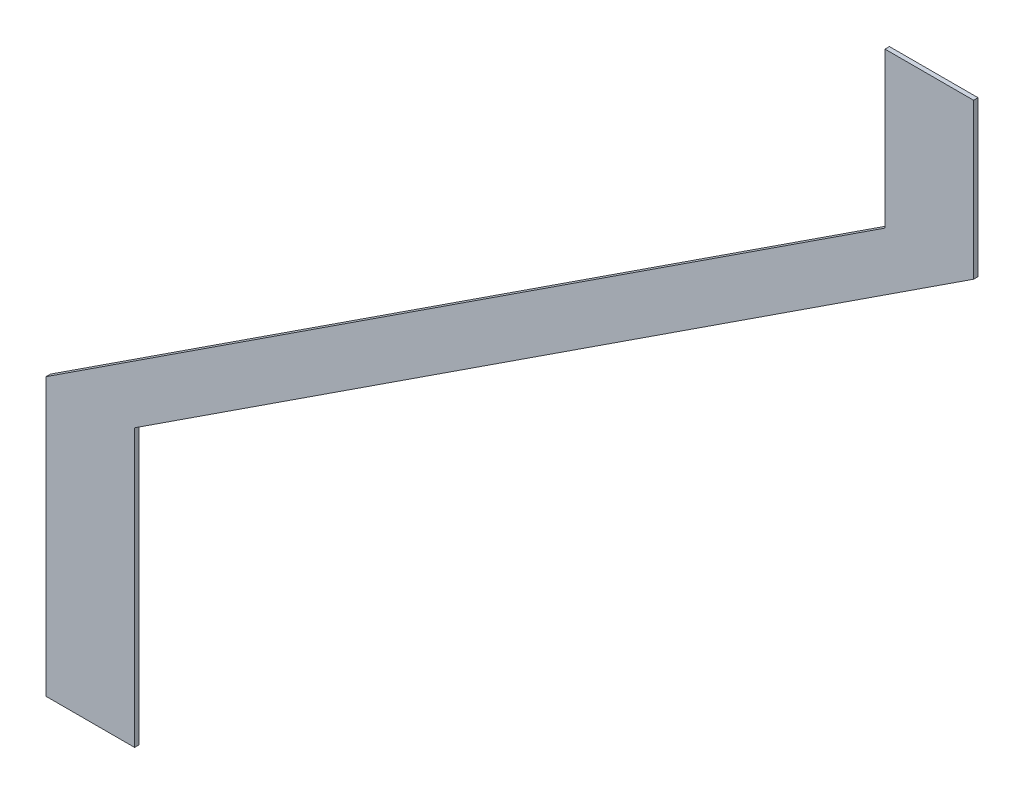
SolidWorks part; units mm, degrees
material "天然橡胶"
ref_plane "前视基准面" through (0, 0, 0) normal (0, 0, 1) x (1, 0, 0)
ref_plane "上视基准面" through (0, 0, 0) normal (0, 1, 0) x (1, 0, 0)
ref_plane "右视基准面" through (0, 0, 0) normal (1, 0, 0) x (0, 0, -1)
sketch "草图1" plane through (0, 0, 0) normal (0, 1, 0) x (1, 0, 0)
  line L0 (0, 1.5) -> (0, -1.5) construction
  line L1 (-991.5, 0) -> (991.5, 0) construction
  line L2 (0, -1.5) -> (-991.4989, -1.5) construction
  line L3 (0, -1.5) -> (991.4989, -1.5) construction
  line L4 (0, 0) -> (-701.0964, -701.0964) construction
  line L5 (-1011.2715, -1.5) -> (-1071.5, -1.5)
  circle A0 centre (0, 0) radius 991.5 construction
  arc A2 (-991.276, -21.0749) -> (-701.0964, -701.0964) centre (0, 0) ccw
  arc A3 (-1011.2715, -1.5) -> (-991.276, -21.0749) centre (-1011.2715, -21.5) cw
  dimension "D1" = 1983
  dimension "D5" = 20
  dimension "D2" = 3
  dimension "D3" = 45
  dimension "D4" = 80
ref_plane "基准面1" through (0, -495, 0) normal (0, 1, 0) x (1, 0, 0)
sketch "草图7" plane through (0, -495, 0) normal (0, 1, 0) x (1, 0, 0)
  line L0 (-1750, -2) -> (1750, -2) construction
  line L1 (-1650, -1750) -> (1650, -1750) construction
  line L2 (-1750, -1750) -> (-1750, 1650) construction
  line L3 (-1650, 1750) -> (1650, 1750) construction
  line L4 (1750, -1650) -> (1750, 1650) construction
  line L5 (-1750, -1750) -> (1750, 1750) construction
  line L6 (-1750, 1750) -> (1750, -1750) construction
  line L7 (-1750, -22) -> (-1750, -1650)
  line L8 (-1770, -2) -> (-1830, -2)
  arc A0 (-1750, -22) -> (-1770, -2) centre (-1770, -22) ccw
  arc A1 (-1750, 1650) -> (-1650, 1750) centre (-1650, 1650) cw construction
  arc A2 (1750, 1650) -> (1650, 1750) centre (1650, 1650) ccw construction
  arc A3 (1750, -1650) -> (1650, -1750) centre (1650, -1650) cw construction
  arc A4 (-1650, -1750) -> (-1750, -1650) centre (-1650, -1650) cw construction
  arc A5 (-1750, -1650) -> (-1720.7107, -1720.7107) centre (-1650, -1650) ccw
  point P0 (0, 0)
  dimension "D5" = 20
  dimension "D6" = 100
  dimension "D1" = 3500
  dimension "D2" = 3500
  dimension "D3" = 2
  dimension "D4" = 80
sketch "草图8" plane through (0, 0, 0) normal (0, 0, 1) x (1, 0, 0)
  line L0 (-1072.3529, 0) -> (-1830, -495)
  line L1 (-1011.2715, 0) -> (-1071.5, 0) construction
  line L2 (-1770, -495) -> (-1830, -495) construction
  line L3 (-1750, -495) -> (-992.3529, 0)
  line L4 (-1750, -495) -> (1750, -495) construction
  line L5 (0, 0) -> (-991.4989, 0) construction
  line L6 (-991.5, 0) -> (991.5, 0) construction
  line L7 (-1650, -495) -> (-1750, -495) construction
  line L8 (-1830, -495) -> (-1830, -745)
  line L9 (-1830, -745) -> (-1750, -745)
  line L10 (-1750, -745) -> (-1750, -495)
  line L11 (-1072.3529, 0) -> (-1072.3529, 140)
  line L12 (-1072.3529, 140) -> (-992.3529, 140)
  line L13 (-992.3529, 140) -> (-992.3529, 0)
  dimension "D1" = 80
  dimension "D2" = 80
  dimension "D3" = 250
  dimension "D4" = 140
base flange "基体-法兰1" sketch "草图8" thickness 4 reverse thickness direction no parameters "D1"=4
ref_plane "基准面2" through (0, 0, -2) normal (0, 0, -1) x (-1, 0, 0)
sketch "折弯-线1" [suppressed] plane through (0, 0, 0) normal (0, 1, 0) x (1, 0, 0)
sketch "边界框1" [suppressed] plane through (0, 0, 0) normal (0, 1, 0) x (1, 0, 0)
sheet metal parameters "钣金6" thickness 4 parameters "D1"=4
flat pattern "平板型式6" [suppressed]
sketch "折弯-线2" plane through (0, 0, 0) normal (0, 1, 0) x (1, 0, 0)
sketch3d "边界框2" [suppressed]
  line L0 (-1791.0856, -784.9853, 0) -> (-914.5246, 68.1002, 0) construction
  line L1 (-1954.954, -616.6075, 0) -> (-1078.393, 236.478, 0) construction
  line L2 (-1791.0856, -784.9853, 0) -> (-1954.954, -616.6075, 0) construction
  line L3 (-914.5246, 68.1002, 0) -> (-1078.393, 236.478, 0) construction
